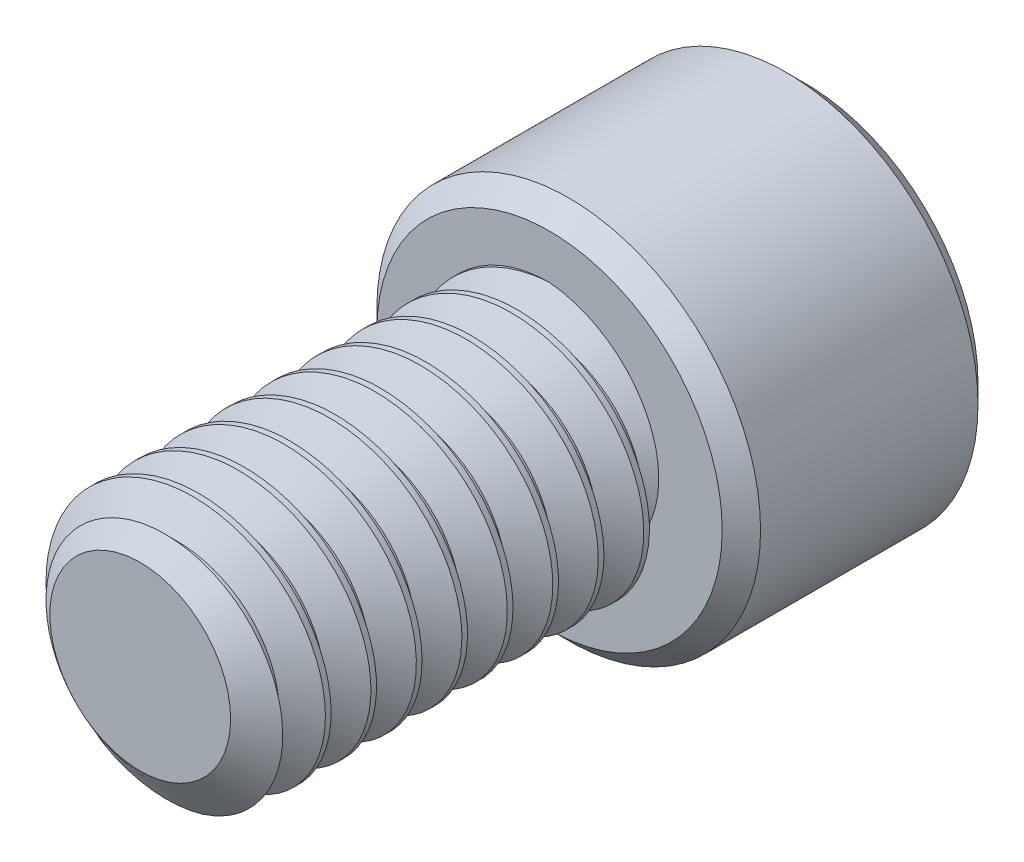
SolidWorks part; units mm, degrees
ref_plane "Front Plane" through (0, 0, 0) normal (0, 0, 1) x (1, 0, 0)
ref_plane "Top Plane" through (0, 0, 0) normal (0, 1, 0) x (1, 0, 0)
ref_plane "Right Plane" through (0, 0, 0) normal (1, 0, 0) x (0, 0, -1)
sketch "Sketch1" plane through (0, 0, 0) normal (0, 0, 1) x (1, 0, 0)
  circle A0 centre (0, 0) radius 3.9751
  dimension "OD" = 7.9502
extrude "Extrude1" add sketch "Sketch1" against normal blind 12.7
sketch "Sketch2" plane through (0, 0, 0) normal (0, 0, 1) x (1, 0, 0)
  circle A0 centre (0, 0) radius 3.9751 construction
  circle A1 centre (0, 0) radius 3.9751
curve "Helix/Spiral1" pitch 1.4111 height 14.1111 turns 10 parameters "pitch"=1.4111
sketch "Sketch3" plane through (0, 0, 0) normal (1, 0, 0) x (0, 0, -1)
  line L0 (-1.2347, 3.9751) -> (-0.7056, 3.0586)
  line L1 (-0.7056, 3.0586) -> (-0.5292, 3.0586)
  line L2 (-0.5292, 3.0586) -> (0, 3.9751)
  line L3 (-1.2347, 3.9751) -> (0, 3.9751)
  line L4 (-0.6174, 3.9751) -> (-0.6174, 3.0586) construction
  line L5 (-0.9701, 3.5168) -> (-0.2646, 3.5168) construction
  line L6 (0, 3.9751) -> (0, -3.9751) construction
  dimension "D1" = 0.1764
  dimension "D2" = 0.7056
  dimension "D3" = 60
sweep "Cut-Sweep1" cut profiles "Sketch3" path "Helix/Spiral1"
sketch "Sketch4" plane through (0, 0, 0) normal (1, 0, 0) x (0, 0, -1)
  line L0 (0.8196, 3.9751) -> (0, 2.8046)
  line L1 (0, 2.8046) -> (0, 3.9751)
  line L2 (0.8196, 3.9751) -> (0, 3.9751)
  line L3 (-1.2347, 3.9751) -> (0, 3.9751) construction
  line L4 (0, 0) -> (7.0209, 0) construction
  dimension "D1" = 55
  dimension "D2" = 0.254
revolve "Cut-Revolve1" cut sketch "Sketch4" angle 360 about L4
sketch "Sketch5" plane through (0, 0, 0) normal (1, 0, 0) x (0, 0, -1)
  line L0 (12.7, -3.0799) -> (12.7, 2.8363) construction
  line L1 (12.7, 4.1021) -> (22.3135, 4.1021)
  line L2 (12.7, 4.1021) -> (12.7, 0)
  line L3 (12.7, 0) -> (22.225, 0)
  line L4 (22.225, 3.7719) -> (22.225, 0)
  line L5 (22.3135, 4.1021) -> (22.225, 3.7719)
  line L6 (0, 0) -> (9.9695, 0) construction
  point P3 (22.225, 4.1021)
  point P10 (22.225, 4.1021)
  dimension "D1" = 0.3302
  dimension "Thread min" = 22.225
  dimension "D2" = 0.127
  dimension "D3" = 15
revolve "partially thread" [suppressed] add sketch "Sketch5" angle 360 about L6
sketch "Sketch6" plane through (0, 0, -12.7) normal (0, 0, -1) x (-1, 0, 0)
  circle A0 centre (0, 0) radius 5.9531
  dimension "head dia" = 11.9062
extrude "Extrude2" add sketch "Sketch6" along normal blind 7.9375
sketch "Sketch7" plane through (0, 0, -20.6375) normal (0, 0, -1) x (-1, 0, 0)
  line L1 (0, 3.6662) -> (-3.175, 1.8331)
  line L2 (-3.175, 1.8331) -> (-3.175, -1.8331)
  line L3 (-3.175, -1.8331) -> (0, -3.6662)
  line L4 (0, -3.6662) -> (3.175, -1.8331)
  line L5 (3.175, -1.8331) -> (3.175, 1.8331)
  line L6 (3.175, 1.8331) -> (0, 3.6662)
  circle A0 centre (0, 0) radius 3.175 construction
  dimension "hex dia" = 6.35
extrude "Cut-Extrude1" cut sketch "Sketch7" against normal blind 4.7625
sketch "Sketch8" plane through (0, 0, -20.6375) normal (0, 0, -1) x (-1, 0, 0)
  circle A0 centre (0, 0) radius 3.6662
extrude "Cut-Extrude2" cut sketch "Sketch8" against normal through all draft 45
chamfer "Chamfer1" distance 0.5953 angle 45 2 edges at (-5.9531, 0, -20.6375) (-5.9531, 0, -12.7)
sketch "Sketch9" plane through (0, 0, 0) normal (1, 0, 0) x (0, 0, -1)
  line L0 (0, 3.9751) -> (0, -3.9751) construction
  line L1 (14.8167, 3.9751) -> (14.8167, -3.9751) construction
  dimension "D1" = 14.8167
equation "\"D3@Helix/Spiral1\" = \"screw length@Extrude1\"+\"pitch@Helix/Spiral1\""
equation "\"D1@Sketch3\" = \"pitch@Helix/Spiral1\"*.125"
equation "\"D2@Sketch3\" = \"pitch@Helix/Spiral1\"*.5"
equation "\"D1@Cut-Extrude1\" = \"hex dia@Sketch7\"*.75"
equation "\"D1@Chamfer1\" = \"head dia@Sketch6\"*.05"
equation "\"D1@Sketch9\" = \"pitch@Helix/Spiral1\"*10.5"
